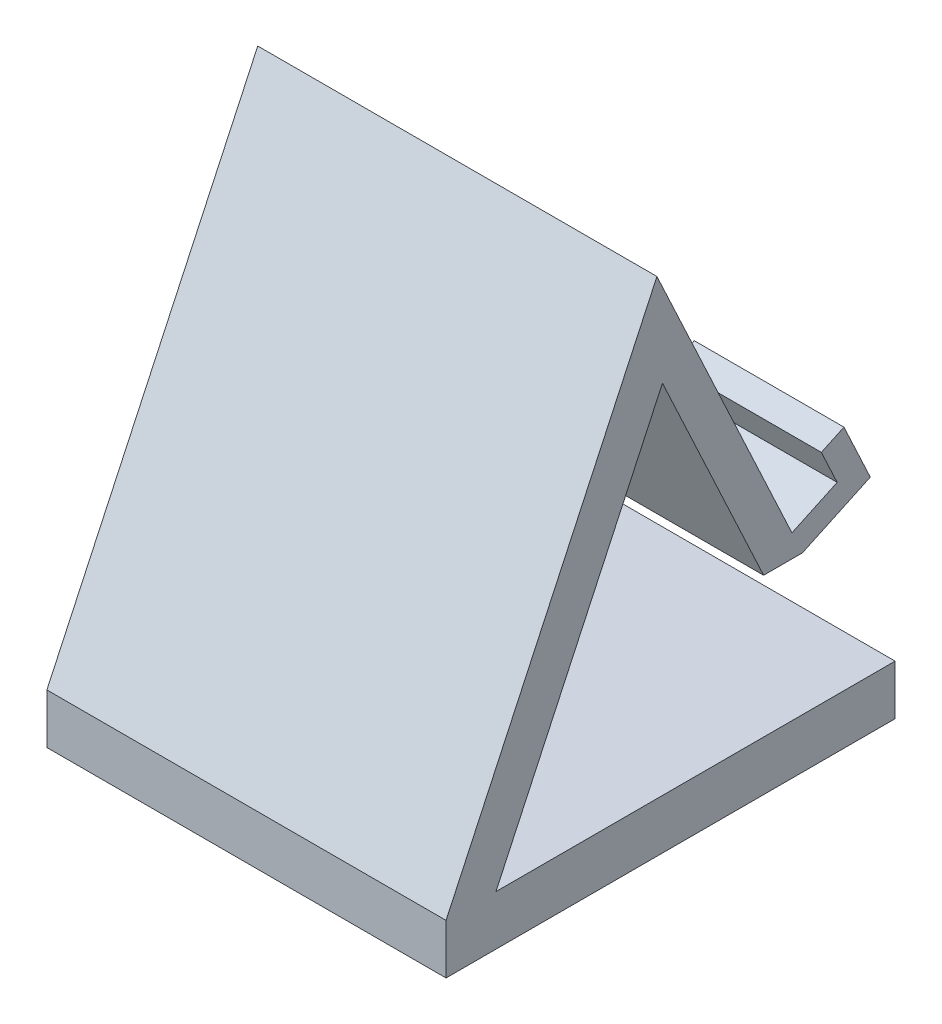
SolidWorks part; units mm, degrees
material "PLA"
ref_plane "Front Plane" through (0, 0, 0) normal (0, 0, 1) x (1, 0, 0)
ref_plane "Top Plane" through (0, 0, 0) normal (0, 1, 0) x (1, 0, 0)
ref_plane "Right Plane" through (0, 0, 0) normal (1, 0, 0) x (0, 0, -1)
other "Center of Mass"
sketch "Sketch1" plane through (0, 0, 0) normal (1, 0, 0) x (0, 0, -1)
  line L0 (0, 10) -> (42.2618, 100.6308)
  line L1 (0, 0) -> (90, 0)
  line L2 (0, 0) -> (0, 10)
  line L3 (10, 10) -> (90, 10)
  line L4 (90, 0) -> (90, 10)
  line L5 (10, 10) -> (43.3688, 81.5597)
  line L6 (42.2618, 100.6308) -> (46.0749, 92.4536)
  line L7 (46.0749, 92.4536) -> (71.432, 38.0752)
  line L8 (43.3688, 81.5597) -> (63.646, 38.0752)
  line L9 (63.646, 38.0752) -> (71.432, 38.0752)
  point P11 (0, 0)
  dimension "D1" = 90
  dimension "D2" = 65
  dimension "D3" = 100
  dimension "D4" = 65
  dimension "D5" = 10
  dimension "D6" = 10
  dimension "D7" = 90
  dimension "D8" = 60
  dimension "D9" = 50
  dimension "D10" = 50
  dimension "D11" = 50
extrude "Boss-Extrude1" add sketch "Sketch1" along normal blind 80
sketch "Sketch2" plane through (0, 34.1605, -73.2574) normal (0, 0.4226, -0.9063) x (-1, 0, 0)
  line L1 (-80, 4.3194) -> (-50, 4.3194)
  line L2 (-80, 4.3194) -> (-80, 9.3194)
  line L3 (-80, 9.3194) -> (-50, 9.3194)
  line L4 (-50, 4.3194) -> (-50, 9.3194)
  line L5 (0, 4.3194) -> (-30, 4.3194)
  line L6 (0, 4.3194) -> (0, 9.3194)
  line L7 (0, 9.3194) -> (-30, 9.3194)
  line L8 (-30, 4.3194) -> (-30, 9.3194)
  dimension "D1" = 30
  dimension "D2" = 5
  dimension "D3" = 30
  dimension "D4" = 5
extrude "Boss-Extrude2" add sketch "Sketch2" along normal blind 10
sketch "Sketch3" plane through (0, 38.3867, -82.3205) normal (0, 0.4226, -0.9063) x (-1, 0, 0)
  line L1 (-80, 4.3194) -> (-50, 4.3194)
  line L2 (-80, 4.3194) -> (-80, 16.8194)
  line L3 (-80, 16.8194) -> (-50, 16.8194)
  line L4 (-50, 4.3194) -> (-50, 16.8194)
  line L5 (-30, 4.3194) -> (0, 4.3194)
  line L6 (-30, 4.3194) -> (-30, 16.8194)
  line L7 (-30, 16.8194) -> (0, 16.8194)
  line L8 (0, 4.3194) -> (0, 16.8194)
  dimension "D1" = 12.5
  dimension "D2" = 30
  dimension "D3" = 30
  dimension "D4" = 12.5
extrude "Boss-Extrude3" add sketch "Sketch3" along normal blind 5
